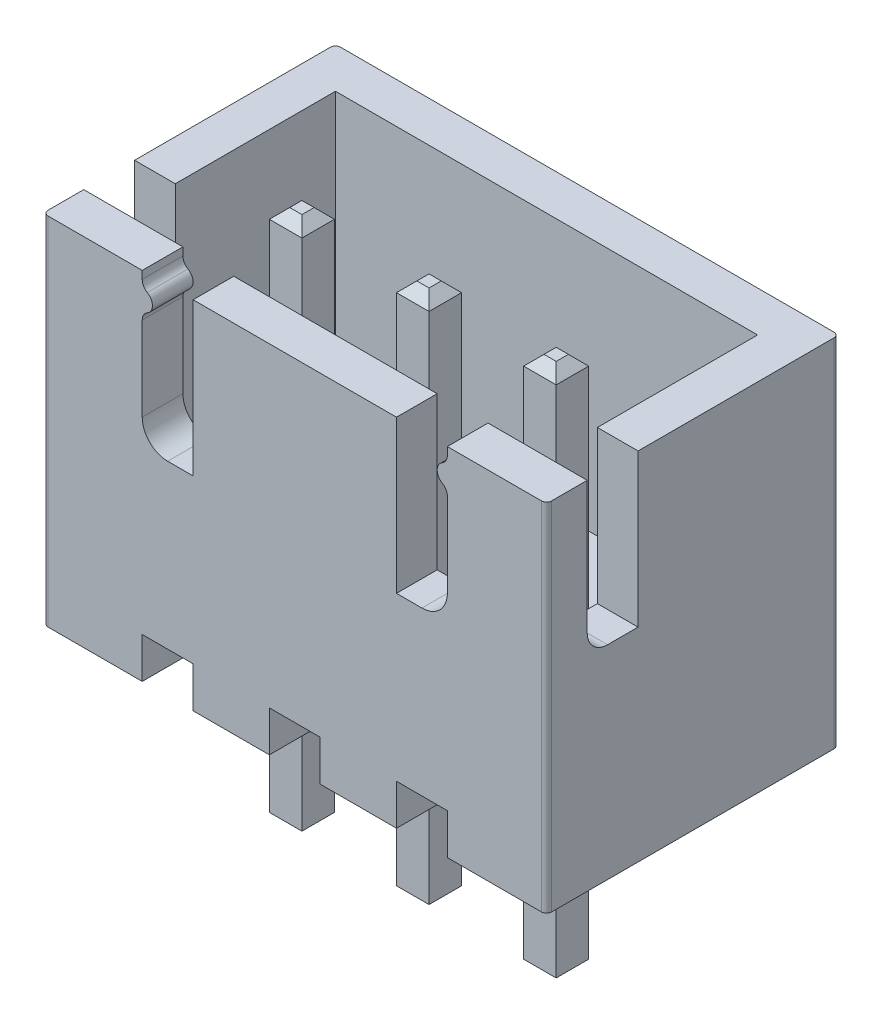
SolidWorks part; units mm, degrees
ref_plane "Спереди" through (0, 0, 0) normal (0, 0, 1) x (1, 0, 0)
ref_plane "Сверху" through (0, 0, 0) normal (0, 1, 0) x (1, 0, 0)
ref_plane "Справа" through (0, 0, 0) normal (1, 0, 0) x (0, 0, -1)
sketch "Эскиз1" plane through (0, 0, 0) normal (0, 1, 0) x (1, 0, 0)
  line L1 (0, 0) -> (9.9, 0)
  line L2 (0, 0) -> (0, 5.75)
  line L3 (0, 5.75) -> (9.9, 5.75)
  line L4 (9.9, 0) -> (9.9, 5.75)
  dimension "D1" = 5.75
  dimension "D2" = 9.9
extrude "Бобышка-Вытянуть1" add sketch "Эскиз1" along normal blind 7
sketch "Эскиз2" plane through (0, 7, 0) normal (0, 1, 0) x (1, 0, 0)
  line L8 (0.8, 4.95) -> (0.8, 0.8)
  line L9 (0.8, 0.8) -> (9.1, 0.8)
  line L10 (9.1, 0.8) -> (9.1, 4.95)
  line L11 (9.1, 4.95) -> (0.8, 4.95)
  line L12 (0.8, 4.95) -> (0.8, 0.8)
  line L13 (0.8, 0.8) -> (9.1, 0.8)
  line L14 (9.1, 0.8) -> (9.1, 4.95)
  line L15 (9.1, 4.95) -> (0.8, 4.95)
  dimension "D1" = 0.8
extrude "Вырез-Вытянуть1" cut sketch "Эскиз2" against normal offset from surface (5 mm away) 2 up to face at (4.95, 0, -2.875)
sketch "Эскиз3" plane through (0, 0, 0) normal (0, 0, 1) x (1, 0, 0)
  line L0 (0, 0) -> (9.9, 0) construction
  line L1 (1.95, 0) -> (2.95, 0)
  line L2 (1.95, 0) -> (1.95, 0.8)
  line L3 (1.95, 0.8) -> (2.95, 0.8)
  line L4 (2.95, 0) -> (2.95, 0.8)
  line L5 (0, 7) -> (0, 0) construction
  line L6 (4.45, 0.8) -> (5.45, 0.8)
  line L7 (5.45, 0) -> (5.45, 0.8)
  line L8 (4.45, 0) -> (4.45, 0.8)
  line L9 (4.45, 0) -> (5.45, 0)
  line L10 (6.95, 0.8) -> (7.95, 0.8)
  line L11 (7.95, 0) -> (7.95, 0.8)
  line L12 (6.95, 0) -> (6.95, 0.8)
  line L13 (6.95, 0) -> (7.95, 0)
  dimension "D1" = 0.8
  dimension "D2" = 1
  dimension "D3" = 1.95
  dimension "D5" = 1.5
  dimension "D4" = 3
extrude "Вырез-Вытянуть2" cut sketch "Эскиз3" against normal up to next
sketch "Эскиз4" plane through (0, 2, 0) normal (0, 1, 0) x (1, 0, 0)
  line L0 (0, 5.75) -> (0, 0) construction
  line L1 (2.13, 2.32) -> (2.77, 2.32)
  line L2 (2.13, 2.32) -> (2.13, 2.96)
  line L3 (2.13, 2.96) -> (2.77, 2.96)
  line L4 (2.77, 2.32) -> (2.77, 2.96)
  line L5 (0, 0) -> (9.9, 0) construction
  dimension "D1" = 0.64
  dimension "D2" = 2.13
  dimension "D3" = 2.32
extrude "Бобышка-Вытянуть2" add sketch "Эскиз4" along normal up to surface (5 mm away) and the other way blind 5.5 up to face at (4.95, 7, -2.875)
chamfer "Фаска1" distance 0.2 angle 45 8 edges at (2.13, 7, -2.64) (2.45, 7, -2.96) (2.77, 7, -2.64) (2.45, 7, -2.32) (2.45, -3.5, -2.32) (2.77, -3.5, -2.64) (2.45, -3.5, -2.96) (2.13, -3.5, -2.64)
pattern_linear "Линейный массив4" count 3 spacing 2.5 along (1, 0, 0) of "Бобышка-Вытянуть2", "Фаска1"
sketch "Эскиз5" plane through (0, 0, 0) normal (0, 0, 1) x (1, 0, 0)
  line L0 (0, 7) -> (9.9, 7) construction
  line L1 (1.95, 7) -> (2.95, 7)
  line L2 (1.95, 7) -> (1.95, 6.8464)
  line L3 (2.45, 4) -> (2.95, 4)
  line L4 (2.95, 7) -> (2.95, 4)
  line L6 (6.95, 7) -> (7.95, 7)
  line L7 (6.95, 7) -> (6.95, 4)
  line L8 (6.95, 4) -> (7.45, 4)
  line L9 (7.95, 7) -> (7.95, 6.8464)
  line L13 (7.95, 6.1536) -> (7.95, 4.5)
  line L14 (1.95, 6.1536) -> (1.95, 4.5)
  line L16 (0, 7) -> (0, 0) construction
  line L17 (9.9, 7) -> (9.9, 0) construction
  arc A0 (7.45, 4) -> (7.95, 4.5) centre (7.45, 4.5) ccw
  arc A1 (1.95, 4.5) -> (2.45, 4) centre (2.45, 4.5) ccw
  arc A2 (1.95, 6.8464) -> (2.05, 6.6732) centre (2.15, 6.8464) ccw
  arc A3 (2.05, 6.6732) -> (2.05, 6.3268) centre (1.95, 6.5) cw
  arc A4 (2.05, 6.3268) -> (1.95, 6.1536) centre (2.15, 6.1536) ccw
  arc A5 (7.95, 6.8464) -> (7.85, 6.6732) centre (7.75, 6.8464) cw
  arc A6 (7.85, 6.6732) -> (7.85, 6.3268) centre (7.95, 6.5) ccw
  arc A7 (7.85, 6.3268) -> (7.95, 6.1536) centre (7.75, 6.1536) cw
  point P22 (1.95, 4)
  dimension "D2" = 0.5
  dimension "D3" = 0.5
  dimension "D4" = 0.2
  dimension "D1" = 3
  dimension "D5" = 1
  dimension "D6" = 1.95
  dimension "D7" = 1.95
extrude "Вырез-Вытянуть3" cut sketch "Эскиз5" against normal up to next
sketch "Эскиз6" plane through (9.9, 0, 0) normal (1, 0, 0) x (0, 0, -1)
  line L0 (0, 7) -> (5.75, 7) construction
  line L1 (0.8, 7) -> (1.8, 7)
  line L2 (0.8, 7) -> (0.8, 4.4)
  line L3 (1.2, 4) -> (1.8, 4)
  line L4 (1.8, 7) -> (1.8, 4)
  line L5 (0.8, 4) -> (0, 4) construction
  arc A0 (0.8, 4.4) -> (1.2, 4) centre (1.2, 4.4) ccw
  dimension "D2" = 0.4
  dimension "D1" = 1
extrude "Вырез-Вытянуть4" cut sketch "Эскиз6" against normal through all
fillet "Скругление1" radius 0.1 4 edges at (0, 3.5, -5.75) (9.9, 3.5, -5.75) (0, 3.5, 0) (9.9, 3.5, 0)
equation "\"N\"= 3'Pin number"
equation "\"D2@Эскиз1\"=2.45 * 2 + 2.5 *(\"N\"-1)"
equation "\"D3@Эскиз3\"=2.45-\"D2@Эскиз3\"/2"
equation "\"D4@Эскиз3\"=\"N\""
equation "\"D2@Эскиз4\"=2.45-\"D1@Эскиз4\"/2"
equation "\"D3@Эскиз4\"=2+\"D1@Эскиз4\"/2"
equation "\"D1@Линейный массив4\"=\"N\""
equation "\"D5@Эскиз5\"=\"D2@Эскиз3\""
equation "\"D6@Эскиз5\"=\"D3@Эскиз3\""
equation "\"D7@Эскиз5\"=\"D6@Эскиз5\""
